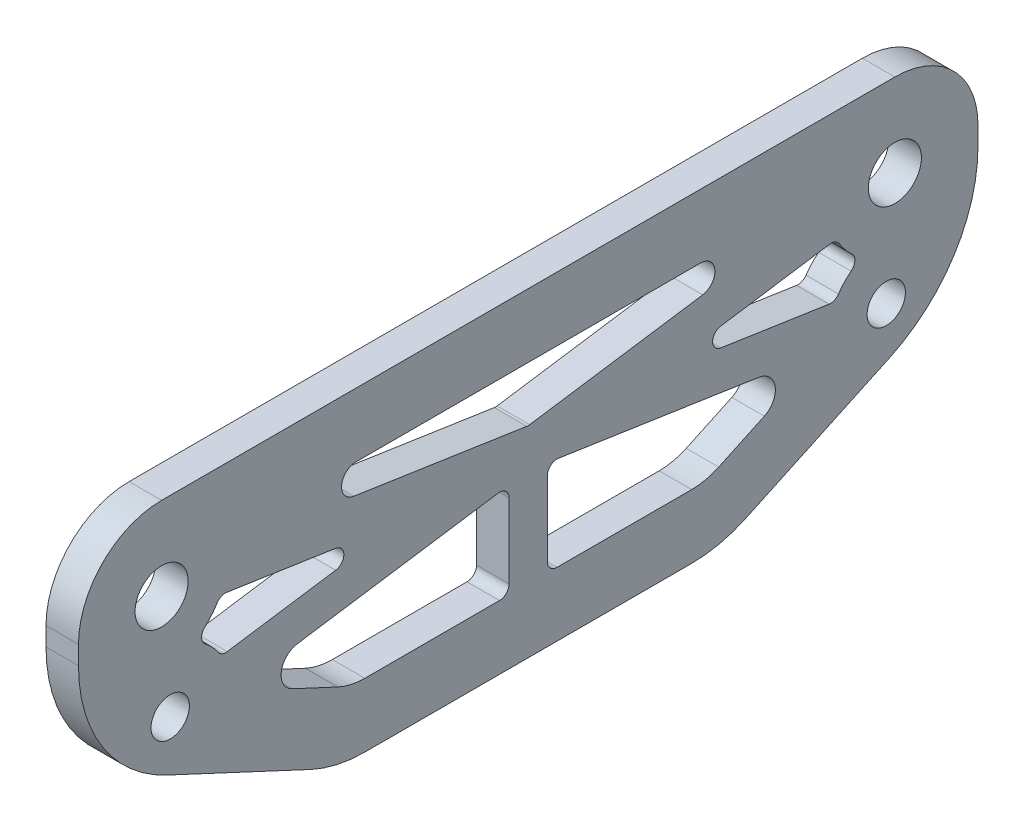
SolidWorks part; units mm, degrees
ref_plane "Front Plane" through (0, 0, 0) normal (0, 0, 1) x (1, 0, 0)
ref_plane "Top Plane" through (0, 0, 0) normal (0, 1, 0) x (1, 0, 0)
ref_plane "Right Plane" through (0, 0, 0) normal (1, 0, 0) x (0, 0, -1)
sketch "Sketch1" plane through (0, 0, 0) normal (1, 0, 0) x (0, 0, -1)
  line L0 (15, 12.5) -> (28.675, 12.5)
  line L1 (-15, -12.5) -> (15, -12.5)
  line L3 (-15, 12.5) -> (15, 12.5)
  line L5 (-15, -12.5) -> (15, 12.5) construction
  line L6 (-15, 12.5) -> (15, -12.5) construction
  line L8 (0, 12.5) -> (0, -12.5) construction
  line L10 (-15, 12.5) -> (-28.675, 12.5)
  line L11 (23.175, 143.1395) -> (23.175, -84.2605) construction
  line L13 (35.175, 6) -> (35.175, 4.5526)
  line L14 (28.2464, -6.3231) -> (15, -12.5)
  line L16 (-35.175, 6) -> (-35.175, 4.5526)
  line L17 (-28.2464, -6.3231) -> (-15, -12.5)
  arc A0 (28.675, 12.5) -> (35.175, 6) centre (28.675, 6) cw
  circle A1 centre (28.675, 6) radius 5.5 construction
  circle A2 centre (-28.675, 6) radius 5.5 construction
  arc A3 (-28.675, 12.5) -> (-35.175, 6) centre (-28.675, 6) ccw
  arc A4 (35.175, 4.5526) -> (28.2464, -6.3231) centre (23.175, 4.5526) cw
  circle A5 centre (28.675, 6) radius 2.075
  arc A6 (-35.175, 4.5526) -> (-28.2464, -6.3231) centre (-23.175, 4.5526) ccw
  circle A9 centre (-28.675, 6) radius 2.075
  circle A11 centre (28, -2.5) radius 1.5
  circle A12 centre (-28, -2.5) radius 1.5
  point P0 (0, 0)
  point P28 (0, 0)
  dimension "D1" = 11
  dimension "D2" = 1
  dimension "D3" = 4.15
  dimension "D4" = 3
  dimension "D6" = 25
  dimension "D8" = 12
  dimension "D5" = 25
  dimension "D7" = 30
  dimension "D9" = 28
  dimension "D10" = 2.5
extrude "Boss-Extrude1" add sketch "Sketch1" along normal blind 2.54
fillet "Fillet1" radius 10 2 edges at (1.27, -12.5, -15) (1.27, -12.5, 15)
sketch "Sketch2" plane through (0, 0, 0) normal (1, 0, 0) x (0, 0, -1)
  line L0 (-28.675, 6) -> (28, -2.5) construction
  line L10 (-28.675, -2.6012) -> (28.675, 6)
  line L11 (-28.675, 6) -> (28, -2.5)
  line L12 (-28.8975, 4.5166) -> (27.7775, -3.9834)
  line L13 (-28.4525, 7.4834) -> (28.2225, -1.0166)
  line L14 (-28.8975, 4.5166) -> (-28.4525, 7.4834)
  line L15 (27.7775, -3.9834) -> (28.2225, -1.0166)
  line L16 (-12.7831, -7.5) -> (12.7831, -7.5)
  line L17 (14.8961, -7.0315) -> (26.1333, -1.7916)
  line L18 (30.175, 4.5526) -> (30.175, 6)
  line L19 (28.675, 7.5) -> (-28.675, 7.5)
  line L20 (-30.175, 6) -> (-30.175, 4.5526)
  line L21 (-26.1333, -1.7916) -> (-14.8961, -7.0315)
  line L22 (-12.7831, -7.5) -> (12.7831, -7.5)
  line L23 (14.8961, -7.0315) -> (26.1333, -1.7916)
  line L24 (30.175, 4.5526) -> (30.175, 6)
  line L25 (28.675, 7.5) -> (-28.675, 7.5)
  line L26 (-30.175, 6) -> (-30.175, 4.5526)
  line L27 (-26.1333, -1.7916) -> (-14.8961, -7.0315)
  line L28 (-28.4525, -4.0846) -> (28.8975, 4.5166)
  line L29 (-28.8975, -1.1178) -> (28.4525, 7.4834)
  line L30 (-28.4525, -4.0846) -> (-28.8975, -1.1178)
  line L31 (28.8975, 4.5166) -> (28.4525, 7.4834)
  line L32 (0, -7.5) -> (0, 7.5) construction
  line L33 (0, 1.6994) -> (0, -7.5)
  line L34 (-1.5, 1.6994) -> (-1.5, -7.5)
  line L35 (1.5, 1.6994) -> (1.5, -7.5)
  line L36 (-1.5, 1.6994) -> (1.5, 1.6994)
  line L37 (-1.5, -7.5) -> (1.5, -7.5)
  arc A0 (-18.0527, -2.5249) -> (-18.4641, -5.3678) centre (-17.8302, -4.0083) ccw
  arc A1 (18.0527, -2.5249) -> (18.4641, -5.3678) centre (17.8302, -4.0083) cw
  circle A2 centre (-28, -2.5) radius 4.5
  circle A3 centre (-28, -2.5) radius 4.5
  circle A5 centre (28, -2.5) radius 4.5
  circle A6 centre (28, -2.5) radius 4.5
  circle A11 centre (-28.675, 6) radius 5.075
  arc A12 (12.7831, -7.5) -> (14.8961, -7.0315) centre (12.7831, -2.5) ccw
  arc A13 (26.1333, -1.7916) -> (30.175, 4.5526) centre (23.175, 4.5526) ccw
  arc A14 (30.175, 6) -> (28.675, 7.5) centre (28.675, 6) ccw
  arc A15 (-28.675, 7.5) -> (-30.175, 6) centre (-28.675, 6) ccw
  arc A16 (-30.175, 4.5526) -> (-26.1333, -1.7916) centre (-23.175, 4.5526) ccw
  arc A17 (-14.8961, -7.0315) -> (-12.7831, -7.5) centre (-12.7831, -2.5) ccw
  arc A18 (12.7831, -7.5) -> (14.8961, -7.0315) centre (12.7831, -2.5) ccw
  arc A19 (26.1333, -1.7916) -> (30.175, 4.5526) centre (23.175, 4.5526) ccw
  arc A20 (30.175, 6) -> (28.675, 7.5) centre (28.675, 6) ccw
  arc A21 (-28.675, 7.5) -> (-30.175, 6) centre (-28.675, 6) ccw
  arc A22 (-30.175, 4.5526) -> (-26.1333, -1.7916) centre (-23.175, 4.5526) ccw
  arc A23 (-14.8961, -7.0315) -> (-12.7831, -7.5) centre (-12.7831, -2.5) ccw
  circle A24 centre (-28.675, 6) radius 5.075
  circle A26 centre (28.675, 6) radius 5.075
  circle A27 centre (28.675, 6) radius 5.075
  arc A32 (13.477, 7.5) -> (13.6439, 5.2624) centre (13.477, 6.375) cw
  arc A33 (-13.477, 7.5) -> (-13.6439, 5.2624) centre (-13.477, 6.375) ccw
  dimension "D11" = 3
  dimension "D12" = 1.125
  dimension "D2" = 1.5
  dimension "D1" = 5
  dimension "D3" = 3
  dimension "D4" = 3
  dimension "D6" = 1.5
  dimension "D7" = 1.5
  dimension "D8" = 1.5
  dimension "D9" = 1.5
  dimension "D13" = 1.5
  dimension "D14" = 1.5
  dimension "D15" = 3
extrude "Cut-Extrude2" cut sketch "Sketch2" along normal through all contours A24 A3 L29 L12 | A27 L28 L13 A6 | L25 A33 L13 L29 A32 | A1 L12 L35 L22 | L28 A0 L22 L34 region at (0, 1.7005, 19.9688) region at (0, -4.2389, 9.1911) region at (0, 5.8357, 0) region at (0, -4.2389, -9.1911) region at (0, 1.7005, -19.9688)
fillet "Fillet2" radius 0.75 13 edges at (1.27, -7.5, -1.5) (1.27, 3.7975, -24.1028) (1.27, 1.6994, -10.1133) (1.27, 3.7975, 24.1028) (1.27, 3.2162, 0) (1.27, -0.0424, -1.5) (1.27, -7.5, 1.5) (1.27, -0.0424, 1.5) (1.27, 1.6994, 10.1133) (1.27, -0.3873, -24.0268) (1.27, 1.6002, -26.1457) (1.27, -0.3873, 24.0268) (1.27, 1.6002, 26.1457)
